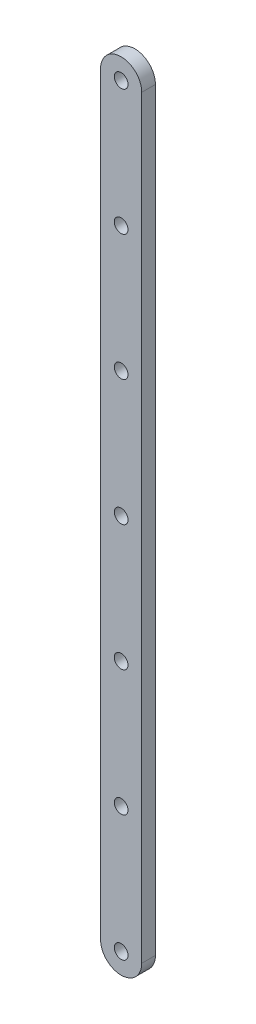
SolidWorks part; units mm, degrees
ref_plane "Front Plane" through (0, 0, 0) normal (1, 0, 0) x (0, 1, 0)
ref_plane "Top Plane" through (0, 0, 0) normal (0, 0, 1) x (0, 1, 0)
ref_plane "Right Plane" through (0, 0, 0) normal (0, 1, 0) x (-1, 0, 0)
sketch "Sketch2" plane through (0, 0, 0) normal (0, 0, 1) x (0, 1, 0)
  line L0 (-275, 15) -> (275, 15)
  line L1 (-275, -15) -> (275, -15)
  arc A0 (-275, 15) -> (-275, -15) centre (-275, 0) ccw
  arc A1 (275, 15) -> (275, -15) centre (275, 0) cw
  circle A2 centre (-275, 0) radius 5
  circle A7 centre (-183.3333, 0) radius 5
  circle A8 centre (-91.6667, 0) radius 5
  circle A9 centre (0, 0) radius 5
  circle A10 centre (91.6667, 0) radius 5
  circle A11 centre (183.3333, 0) radius 5
  circle A12 centre (275, 0) radius 5
  point P6 (0, -15)
  dimension "D1" = 30
  dimension "D3" = 10
  dimension "D4" = 7
  dimension "D2" = 550
extrude "Boss-Extrude1" add sketch "Sketch2" along normal blind 10
